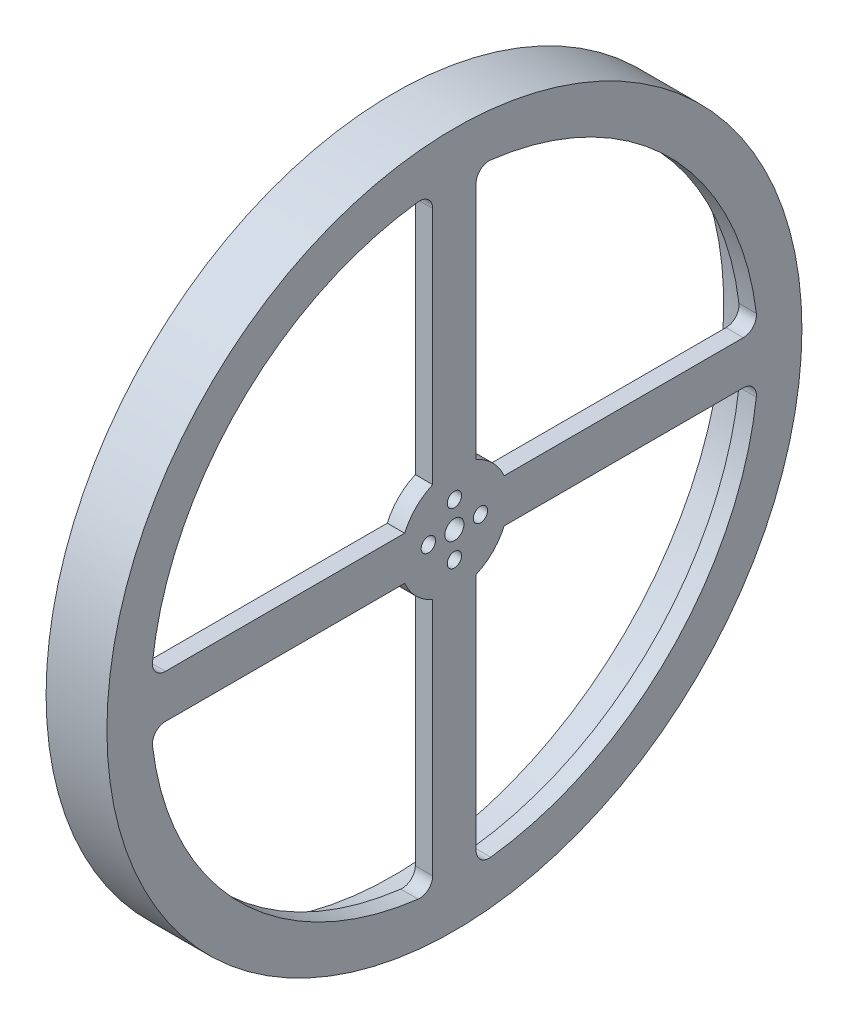
SolidWorks part; units mm, degrees
ref_plane "Front Plane" through (0, 0, 0) normal (1, 0, 0) x (0, 1, 0)
ref_plane "Top Plane" through (0, 0, 0) normal (0, 0, 1) x (0, 1, 0)
ref_plane "Right Plane" through (0, 0, 0) normal (0, 1, 0) x (-1, 0, 0)
sketch "Sketch3" plane through (0, 0, 0) normal (1, 0, 0) x (0, 1, 0)
  circle A0 centre (0, 0) radius 80
  dimension "D1" = 160
extrude "Boss-Extrude3" add sketch "Sketch3" along normal blind 4
sketch "Sketch5" plane through (4, 0, 0) normal (1, 0, 0) x (0, 1, 0)
  circle A0 centre (0, 6) radius 1.65
  circle A1 centre (6, 0) radius 1.65
  circle A2 centre (0, -6) radius 1.65
  circle A3 centre (-6, 0) radius 1.65
  point P2 (3.7475, -8.2815)
  point P12 (0, 0)
  dimension "D1" = 3.3
  dimension "D2" = 6
  dimension "D3" = 4
extrude "Cut-Extrude3" cut sketch "Sketch5" against normal through all
sketch "Sketch6" plane through (4, 0, 0) normal (1, 0, 0) x (0, 1, 0)
  line L0 (11.4564, 5) -> (69.8212, 5)
  line L1 (5, 11.4564) -> (5, 69.8212)
  arc A0 (5, 69.8212) -> (69.8212, 5) centre (0, 0) cw
  arc A1 (5, 11.4564) -> (11.4564, 5) centre (0, 0) cw
  dimension "D1" = 70
  dimension "D4" = 12.5
  dimension "D2" = 5
  dimension "D3" = 5
extrude "Cut-Extrude4" cut sketch "Sketch6" against normal through all
pattern_circular "CirPattern2" count 4 over 360 about axis through (4, 0, 0) along (-1, 0, 0) of "Cut-Extrude4"
fillet "Fillet2" radius 3 8 edges at (2, -5, 69.8212) (2, 5, 69.8212) (2, -69.8212, 5) (2, -69.8212, -5) (2, -5, -69.8212) (2, 5, -69.8212) (2, 69.8212, -5) (2, 69.8212, 5)
sketch "Sketch7" plane through (0, 0, 0) normal (-1, 0, 0) x (0, -1, 0)
  circle A0 centre (0, 0) radius 80
  circle A1 centre (0, 0) radius 80 construction
  circle A2 centre (0, 0) radius 76
  dimension "D1" = 4
extrude "Boss-Extrude4" add sketch "Sketch7" along normal blind 10
sketch "Sketch8" plane through (4, 0, 0) normal (1, 0, 0) x (0, 1, 0)
  circle A0 centre (0, 0) radius 2.2
  dimension "D1" = 4.4
extrude "Cut-Extrude5" cut sketch "Sketch8" against normal through all
